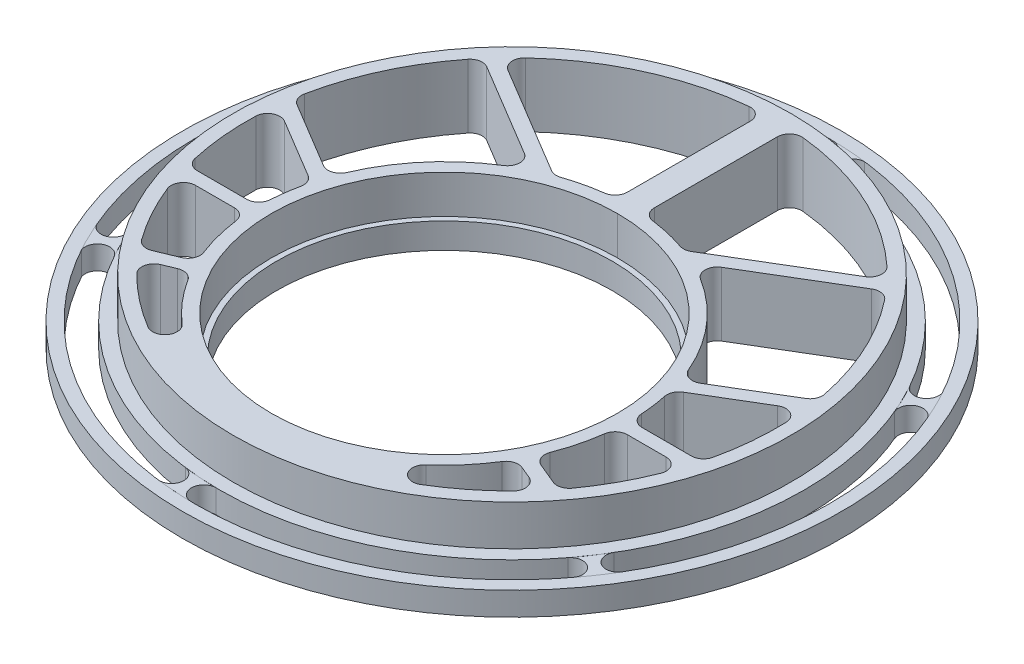
SolidWorks part; units mm, degrees
material "6061-T6 (SS)"
ref_plane "X-Y Datum" through (0, 0, 0) normal (0, 0, 1) x (1, 0, 0)
ref_plane "X-Z Datum" through (0, 0, 0) normal (0, 1, 0) x (1, 0, 0)
ref_plane "Y-Z Datum" through (0, 0, 0) normal (1, 0, 0) x (0, 0, -1)
sketch "Sketch1" plane through (0, 0, 0) normal (0, 1, 0) x (1, 0, 0)
  line L0 (0, 0) -> (0, -12.7) construction
  line L1 (0, -43.0151) -> (0, 43.0151) construction
  line L2 (0, 52.3875) -> (0, 61.9125) construction
  circle A0 centre (0, -12.7) radius 30.988
  circle A1 centre (0, 0) radius 52.3875 construction
  circle A2 centre (0, 0) radius 61.9125
  circle A3 centre (0, 0) radius 57.15 construction
  point P12 (0, 57.15)
  dimension "D2" = 61.976
  dimension "D3" = 104.775
  dimension "D4" = 123.825
  dimension "D5" = 114.3
  dimension "D1" = 12.7
extrude "Slotted-Body Extrude" add sketch "Sketch1" along normal blind 4.191 and the other way blind 0.2032
sketch "Sketch5" plane through (0, 4.191, 0) normal (0, 1, 0) x (1, 0, 0)
  circle A0 centre (0, 0) radius 52.3875 construction
  circle A1 centre (0, 0) radius 52.3875
extrude "Boss-Extrude3" add sketch "Sketch5" along normal blind 7.62
sketch "Sketch6" plane through (0, -0.2032, 0) normal (0, -1, 0) x (1, 0, 0)
  line L0 (0, -79.2756) -> (0, 0) construction
  circle A0 centre (0, 12.7) radius 30.988 construction
  circle A1 centre (0, 12.7) radius 30.988 construction
  circle A2 centre (0, 12.7) radius 32.512
  circle A21 centre (0, 0) radius 61.9125 construction
  dimension "D1" = 65.024
extrude "Cut-Extrude5" cut sketch "Sketch6" against normal through all
sketch "Sketch8" plane through (0, -0.2032, 0) normal (0, -1, 0) x (1, 0, 0)
  circle A0 centre (0, 12.7) radius 32.512 construction
  circle A1 centre (0, 12.7) radius 32.512
  circle A2 centre (0, 12.7) radius 31.496
  dimension "D1" = 62.992
extrude "Boss-Extrude4" add sketch "Sketch8" against normal blind 4.795 separate body
ref_point "Point1"
ref_plane "Plane1" through (0, 0, 0) normal (1, 0, 0) x (0, 0, -1)
split line "Split Line1"
ref_point "Point2"
ref_point "Point3"
ref_point "Point5"
ref_plane "Plane2" through (-42.4707, 0, 0) normal (-1, 0, 0) x (0, 0, 1)
ref_plane "Plane3" through (55.9011, 0, 0) normal (-1, 0, 0) x (0, 0, 1)
sketch "Sketch11" plane through (0, -0.2032, 0) normal (0, -1, 0) x (1, 0, 0)
  line L1 (-61.9125, -61.9125) -> (61.9125, -61.9125)
  line L2 (-61.9125, -61.9125) -> (-61.9125, 61.9125)
  line L3 (-61.9125, 61.9125) -> (61.9125, 61.9125)
  line L4 (61.9125, -61.9125) -> (61.9125, 61.9125)
  line L5 (-61.9125, -61.9125) -> (61.9125, 61.9125) construction
  line L6 (-61.9125, 61.9125) -> (61.9125, -61.9125) construction
  circle A0 centre (0, 0) radius 61.9125 construction
  point P0 (0, 0)
ref_point "Point6"
sketch "Sketch12" plane through (0, 4.191, 0) normal (0, 1, 0) x (1, 0, 0)
  arc A0 (-21.7092, 50.4401) -> (-43.7265, 33.2188) centre (0, 0) ccw
  arc A1 (-21.7092, 50.4401) -> (-23.5277, 54.6654) centre (-22.6185, 52.5527) ccw
  circle A2 centre (0, 0) radius 57.2135 construction
  arc A3 (-49.1884, 29.2213) -> (-57.2005, 1.2219) centre (0, 0) ccw construction
  arc A4 (-51.1658, 30.396) -> (-59.4999, 1.271) centre (0, 0) ccw
  arc A5 (-47.211, 28.0466) -> (-54.901, 1.1727) centre (0, 0) ccw
  arc A6 (-47.211, 28.0466) -> (-51.1658, 30.396) centre (-49.1884, 29.2213) ccw
  arc A7 (-59.4999, 1.271) -> (-54.901, 1.1727) centre (-57.2005, 1.2219) ccw
  arc A8 (-47.3894, 36.0014) -> (-43.7265, 33.2188) centre (-45.5579, 34.6101) ccw
  arc A9 (-23.5277, 54.6654) -> (-47.3894, 36.0014) centre (0, 0) ccw
  arc A10 (-22.6185, 52.5527) -> (-45.5579, 34.6101) centre (0, 0) ccw construction
  arc A11 (12.0848, 53.5672) -> (-15.85, 52.5763) centre (0, 0) ccw
  arc A12 (12.0848, 53.5672) -> (13.0972, 58.0545) centre (12.591, 55.8109) ccw
  arc A13 (-17.1777, 56.9805) -> (-15.85, 52.5763) centre (-16.5138, 54.7784) ccw
  arc A14 (13.0972, 58.0545) -> (-17.1777, 56.9805) centre (0, 0) ccw
  arc A15 (12.591, 55.8109) -> (-16.5138, 54.7784) centre (0, 0) ccw construction
  arc A16 (41.2629, 36.2335) -> (18.0807, 51.8515) centre (0, 0) ccw
  arc A17 (41.2629, 36.2335) -> (44.7194, 39.2687) centre (42.9911, 37.7511) ccw
  arc A18 (19.5953, 56.195) -> (18.0807, 51.8515) centre (18.838, 54.0233) ccw
  arc A19 (44.7194, 39.2687) -> (19.5953, 56.195) centre (0, 0) ccw
  arc A20 (42.9911, 37.7511) -> (18.838, 54.0233) centre (0, 0) ccw construction
  arc A21 (54.6799, 5.0598) -> (45.1051, 31.3212) centre (0, 0) ccw
  arc A22 (54.6799, 5.0598) -> (59.2603, 5.4837) centre (56.9701, 5.2717) ccw
  arc A23 (48.8835, 33.9449) -> (45.1051, 31.3212) centre (46.9943, 32.6331) ccw
  arc A24 (59.2603, 5.4837) -> (48.8835, 33.9449) centre (0, 0) ccw
  arc A25 (56.9701, 5.2717) -> (46.9943, 32.6331) centre (0, 0) ccw construction
  arc A26 (47.211, -28.0466) -> (54.901, -1.1727) centre (0, 0) ccw
  arc A27 (47.211, -28.0466) -> (51.1658, -30.396) centre (49.1884, -29.2213) ccw
  arc A28 (59.4999, -1.271) -> (54.901, -1.1727) centre (57.2005, -1.2219) ccw
  arc A29 (51.1658, -30.396) -> (59.4999, -1.271) centre (0, 0) ccw
  arc A30 (49.1884, -29.2213) -> (57.2005, -1.2219) centre (0, 0) ccw construction
  arc A31 (21.7092, -50.4401) -> (43.7265, -33.2188) centre (0, 0) ccw
  arc A32 (21.7092, -50.4401) -> (23.5277, -54.6654) centre (22.6185, -52.5527) ccw
  arc A33 (47.3894, -36.0014) -> (43.7265, -33.2188) centre (45.5579, -34.6101) ccw
  arc A34 (23.5277, -54.6654) -> (47.3894, -36.0014) centre (0, 0) ccw
  arc A35 (22.6185, -52.5527) -> (45.5579, -34.6101) centre (0, 0) ccw construction
  arc A36 (-12.0848, -53.5672) -> (15.85, -52.5763) centre (0, 0) ccw
  arc A37 (-12.0848, -53.5672) -> (-13.0972, -58.0545) centre (-12.591, -55.8109) ccw
  arc A38 (17.1777, -56.9805) -> (15.85, -52.5763) centre (16.5138, -54.7784) ccw
  arc A39 (-13.0972, -58.0545) -> (17.1777, -56.9805) centre (0, 0) ccw
  arc A40 (-12.591, -55.8109) -> (16.5138, -54.7784) centre (0, 0) ccw construction
  arc A41 (-41.2629, -36.2335) -> (-18.0807, -51.8515) centre (0, 0) ccw
  arc A42 (-41.2629, -36.2335) -> (-44.7194, -39.2687) centre (-42.9911, -37.7511) ccw
  arc A43 (-19.5953, -56.195) -> (-18.0807, -51.8515) centre (-18.838, -54.0233) ccw
  arc A44 (-44.7194, -39.2687) -> (-19.5953, -56.195) centre (0, 0) ccw
  arc A45 (-42.9911, -37.7511) -> (-18.838, -54.0233) centre (0, 0) ccw construction
  arc A46 (-54.6799, -5.0598) -> (-45.1051, -31.3212) centre (0, 0) ccw
  arc A47 (-54.6799, -5.0598) -> (-59.2603, -5.4837) centre (-56.9701, -5.2717) ccw
  arc A48 (-48.8835, -33.9449) -> (-45.1051, -31.3212) centre (-46.9943, -32.6331) ccw
  arc A49 (-59.2603, -5.4837) -> (-48.8835, -33.9449) centre (0, 0) ccw
  arc A50 (-56.9701, -5.2717) -> (-46.9943, -32.6331) centre (0, 0) ccw construction
  point P3 (-55.0058, 15.7399)
  point P10 (-48.0137, 31.1987)
  point P15 (-35.249, 45.0655)
  point P22 (-2.0282, 57.1775)
  point P29 (31.9673, 47.4498)
  point P36 (53.7523, 19.5978)
  point P43 (55.0058, -15.7399)
  point P50 (35.249, -45.0655)
  point P57 (2.0282, -57.1775)
  point P62 (0, 0)
  point P65 (-31.9673, -47.4498)
  point P72 (-53.7523, -19.5978)
  dimension "D1" = 114.427
  dimension "D2" = 2.3
  dimension "D3" = 29.9768
  dimension "D4" = 10
sketch "Sketch13" plane through (0, 4.191, 0) normal (0, 1, 0) x (1, 0, 0)
  arc A32 (-45.5579, 34.6101) -> (-49.1884, 29.2213) centre (0, 0) ccw construction
  arc A33 (-47.3894, 36.0014) -> (-51.1658, 30.396) centre (0, 0) ccw
  arc A34 (-43.7265, 33.2188) -> (-47.211, 28.0466) centre (0, 0) ccw
  arc A37 (-47.211, 28.0466) -> (-51.1658, 30.396) centre (-49.1884, 29.2213) ccw
  arc A38 (-47.3894, 36.0014) -> (-43.7265, 33.2188) centre (-45.5579, 34.6101) ccw
  arc A39 (6.905, 54.4776) -> (0.6835, 54.9092) centre (0, 0) ccw
  arc A40 (0.6835, 54.9092) -> (0.7408, 59.5089) centre (0.7121, 57.2091) ccw
  arc A41 (7.4835, 59.0411) -> (0.7408, 59.5089) centre (0, 0) ccw
  arc A42 (7.4835, 59.0411) -> (6.905, 54.4776) centre (7.1943, 56.7594) ccw
  arc A43 (50.6315, 21.2589) -> (47.8946, 26.8627) centre (0, 0) ccw
  arc A44 (47.8946, 26.8627) -> (51.9066, 29.1129) centre (49.9006, 27.9878) ccw
  arc A45 (54.8728, 23.0397) -> (51.9066, 29.1129) centre (0, 0) ccw
  arc A46 (54.8728, 23.0397) -> (50.6315, 21.2589) centre (52.7522, 22.1493) ccw
  arc A47 (43.7265, -33.2188) -> (47.211, -28.0466) centre (0, 0) ccw
  arc A48 (47.211, -28.0466) -> (51.1658, -30.396) centre (49.1884, -29.2213) ccw
  arc A49 (47.3894, -36.0014) -> (51.1658, -30.396) centre (0, 0) ccw
  arc A50 (47.3894, -36.0014) -> (43.7265, -33.2188) centre (45.5579, -34.6101) ccw
  arc A51 (-6.905, -54.4776) -> (-0.6835, -54.9092) centre (0, 0) ccw
  arc A52 (-0.6835, -54.9092) -> (-0.7408, -59.5089) centre (-0.7121, -57.2091) ccw
  arc A53 (-7.4835, -59.0411) -> (-0.7408, -59.5089) centre (0, 0) ccw
  arc A54 (-7.4835, -59.0411) -> (-6.905, -54.4776) centre (-7.1943, -56.7594) ccw
  arc A55 (-50.6315, -21.2589) -> (-47.8946, -26.8627) centre (0, 0) ccw
  arc A56 (-47.8946, -26.8627) -> (-51.9066, -29.1129) centre (-49.9006, -27.9878) ccw
  arc A57 (-54.8728, -23.0397) -> (-51.9066, -29.1129) centre (0, 0) ccw
  arc A58 (-54.8728, -23.0397) -> (-50.6315, -21.2589) centre (-52.7522, -22.1493) ccw
  point P3 (-47.4498, 31.9673)
  point P36 (0, 0)
  point P39 (-1.8493, -2.0918)
  dimension "D1" = 6
sketch "Sketch14" plane through (0, 4.191, 0) normal (0, 1, 0) x (1, 0, 0)
  circle A0 centre (0, 0) radius 54.9135
  circle A1 centre (0, 0) radius 59.5135
extrude "Cut-Extrude6" cut sketch "Sketch14" against normal through all
extrude "Boss-Extrude5" add sketch "Sketch13" against normal through all separate body
sketch "Sketch16" plane through (0, 11.811, 0) normal (0, 1, 0) x (1, 0, 0)
  line L0 (2.54, 47.3005) -> (2.54, 24.209)
  line L4 (37.1539, -12.7) -> (46.3962, -12.7)
  line L5 (11.3204, 20.3394) -> (4.3187, 21.9689)
  line L6 (13.1357, 20.5806) -> (33.5793, 32.8291)
  line L7 (35.3988, -0.013) -> (47.7939, 7.4134)
  line L8 (18.5291, 20.851) -> (36.1558, 31.4118)
  line L9 (11.4323, 20.3134) -> (11.3204, 20.3394)
  line L10 (35.246, -3.0656) -> (46.3382, 3.5803)
  line L11 (34.8325, -15.24) -> (50.1218, -15.24)
  line L12 (31.6638, -27.4363) -> (41.7639, -31.6264)
  line L13 (30.5052, -29.7056) -> (40.1156, -33.6925)
  line L14 (0, 22.225) -> (0, 52.3875)
  line L15 (-30.5052, -29.7056) -> (-40.1156, -33.6925)
  line L16 (-31.6638, -27.4363) -> (-41.7639, -31.6264)
  line L17 (-34.8325, -15.24) -> (-50.1218, -15.24)
  line L18 (-37.1539, -12.7) -> (-46.3962, -12.7)
  line L19 (-35.246, -3.0656) -> (-46.3382, 3.5803)
  line L20 (-35.3988, -0.013) -> (-47.7939, 7.4134)
  line L21 (-18.5291, 20.851) -> (-36.1558, 31.4118)
  line L22 (-13.1357, 20.5806) -> (-33.5793, 32.8291)
  line L23 (-2.54, 47.3005) -> (-2.54, 24.209)
  line L24 (0, -12.7) -> (0, -47.625)
  arc A0 (18.5291, 20.851) -> (18.4933, 16.9269) centre (19.7112, 18.878) ccw
  circle A1 centre (0, 0) radius 52.3875 construction
  circle A2 centre (0, -12.7) radius 34.925
  arc A3 (0, 19.812) -> (0, -45.212) centre (0, -12.7) ccw construction
  circle A4 centre (4.84, 47.3005) radius 2.3
  circle A5 centre (32.3972, 34.8021) radius 2.3
  arc A6 (2.54, 24.209) -> (4.541, 21.9285) centre (4.84, 24.209) ccw
  arc A7 (11.215, 20.3753) -> (13.1357, 20.5806) centre (11.9536, 22.5535) ccw
  circle A8 centre (37.3379, 29.4389) radius 2.3
  arc A9 (32.1026, 1.0542) -> (35.3988, -0.013) centre (34.2167, 1.96) ccw
  arc A10 (34.8583, -10.5421) -> (37.1539, -12.7) centre (37.1539, -10.4) ccw
  circle A11 centre (46.6118, 9.3864) radius 2.3
  circle A12 centre (46.3962, -10.4) radius 2.3
  circle A13 centre (0, 0) radius 52.3875 construction
  circle A14 centre (47.5203, 1.6073) radius 2.3
  arc A15 (35.246, -3.0656) -> (34.1773, -5.5119) centre (36.428, -5.0385) ccw
  arc A16 (36.909, -15.24) -> (34.6285, -17.241) centre (36.909, -17.54) ccw
  circle A17 centre (44.194, -17.54) radius 2.3
  circle A18 centre (38.5665, -27.8099) radius 2.3
  arc A19 (32.5467, -25.3675) -> (33.8088, -28.3262) centre (34.6901, -26.2018) ccw
  circle A20 centre (-44.194, -17.54) radius 2.3
  circle A21 centre (-38.5665, -27.8099) radius 2.3
  arc A22 (-32.5467, -25.3675) -> (-33.8088, -28.3262) centre (-34.6901, -26.2018) cw
  arc A23 (-36.909, -15.24) -> (-34.6285, -17.241) centre (-36.909, -17.54) cw
  arc A24 (-35.246, -3.0656) -> (-34.1773, -5.5119) centre (-36.428, -5.0385) cw
  arc A25 (-34.8583, -10.5421) -> (-37.1539, -12.7) centre (-37.1539, -10.4) cw
  circle A26 centre (-46.3962, -10.4) radius 2.3
  circle A27 centre (-47.5203, 1.6073) radius 2.3
  arc A28 (-32.1026, 1.0542) -> (-35.3988, -0.013) centre (-34.2167, 1.96) cw
  circle A29 centre (-46.6118, 9.3864) radius 2.3
  circle A30 centre (-37.3379, 29.4389) radius 2.3
  arc A31 (-18.5291, 20.851) -> (-18.4933, 16.9269) centre (-19.7112, 18.878) cw
  arc A32 (-2.54, 24.209) -> (-4.541, 21.9285) centre (-4.84, 24.209) cw
  arc A33 (-11.215, 20.3753) -> (-13.1357, 20.5806) centre (-11.9536, 22.5535) cw
  circle A34 centre (-32.3972, 34.8021) radius 2.3
  circle A35 centre (-4.84, 47.3005) radius 2.3
  circle A36 centre (-31.4636, -32.5933) radius 2.3
  circle A37 centre (-33.7149, -33.5272) radius 2.3
  circle A39 centre (0, 0) radius 49.8475
  circle A40 centre (0, 0) radius 49.8475
  circle A41 centre (-24.4134, -40.8013) radius 2.3
  circle A42 centre (33.7149, -33.5272) radius 2.3
  circle A43 centre (31.4636, -32.5933) radius 2.3
  circle A44 centre (24.4134, -40.8013) radius 2.3
  point P56 (35.3104, -31.6991)
  circle M10 centre (0, 0) radius 52.3875
  dimension "D1" = 4.6
  dimension "D2" = 4.6
  dimension "D3" = 4.6
  dimension "D4" = 4.6
  dimension "D5" = 4.6
  dimension "D6" = 4.6
  dimension "D7" = 2.54
  dimension "D8" = 4.6
  dimension "D9" = 4.6
  dimension "D10" = 4.6
  dimension "D11" = 4.6
  dimension "D13" = 4.6
  dimension "D14" = 2.54
  dimension "D16" = 4.6
  dimension "D17" = 4.6
  dimension "D18" = 4.6
  dimension "D19" = 4.6
  dimension "D20" = 2.54
  dimension "D22" = 4.6
  dimension "D23" = 4.6
  dimension "D24" = 4.6
  dimension "D12" = 2.54
  dimension "D15" = 2.54
  dimension "D21" = 2.54
extrude "Cut-Extrude11" cut sketch "Sketch16" against normal through all and the other way through all contours L23 A35 A34 L22 A33 A2 A32 M10 | A2 A7 L6 A5 A4 L0 A6 M10 | A4 | A35 | A8 | A5 | A11 A8 L8 A0 A2 A9 L7 M10 | A11 | L10 A15 A2 A10 L4 A12 A14 M10 | A14 | A12 | A2 A19 L12 A18 A17 L11 A16 M10 | A17 | A18 | A21 | A23 L17 A20 A21 L16 A22 A2 M10 | A20 | L19 A27 A26 L18 A25 A2 A24 M10 | A27 | A26 | A31 L21 A30 A29 L20 A28 A2 M10 | A29 | A30 | A34 | A40 A41 A2 A36 A37 | A44 | A43 A42 | A42 A43 | A42 A43 | A43 A42 L13 | A41 | A37 A36 | A36 A37 | A37 A36 | L15 A37 A36 | A44 A40 A42 A43 A2 region at (14.8594, 11.811, -34.7717) region at (4.84, 11.811, -47.3005) region at (32.3972, 11.811, -34.8021) region at (34.3513, 11.811, -15.7346) region at (37.3379, 11.811, -29.4389) region at (-4.84, 11.811, -47.3005) region at (-14.8594, 11.811, -34.7717) region at (46.6118, 11.811, -9.3864) region at (-32.3972, 11.811, -34.8021) region at (41.8994, 11.811, 5.7289) region at (47.5203, 11.811, -1.6073) region at (-37.3379, 11.811, -29.4389) region at (-34.3513, 11.811, -15.7346) region at (-38.4578, 11.811, 21.7121) region at (-44.194, 11.811, 17.54) region at (-41.8994, 11.811, 5.7289) region at (-46.3962, 11.811, 10.4) region at (-46.6118, 11.811, -9.3864) region at (46.3962, 11.811, 10.4) region at (38.4578, 11.811, 21.7121) region at (44.194, 11.811, 17.54) region at (-47.5203, 11.811, -1.6073) region at (-38.5665, 11.811, 27.8099) region at (38.5665, 11.811, 27.8099) region at (-33.431, 11.811, 31.0312) region at (-34.3437, 11.811, 33.7881) region at (-28.8578, 11.811, 37.245) region at (33.431, 11.811, 31.0312) region at (34.3437, 11.811, 33.7881) region at (28.8578, 11.811, 37.245) region at (-30.8348, 11.811, 32.3324) region at (-32.5892, 11.811, 33.0602) region at (-24.4134, 11.811, 40.8013) region at (30.8348, 11.811, 32.3324) region at (32.5892, 11.811, 33.0602) region at (24.4134, 11.811, 40.8013)
